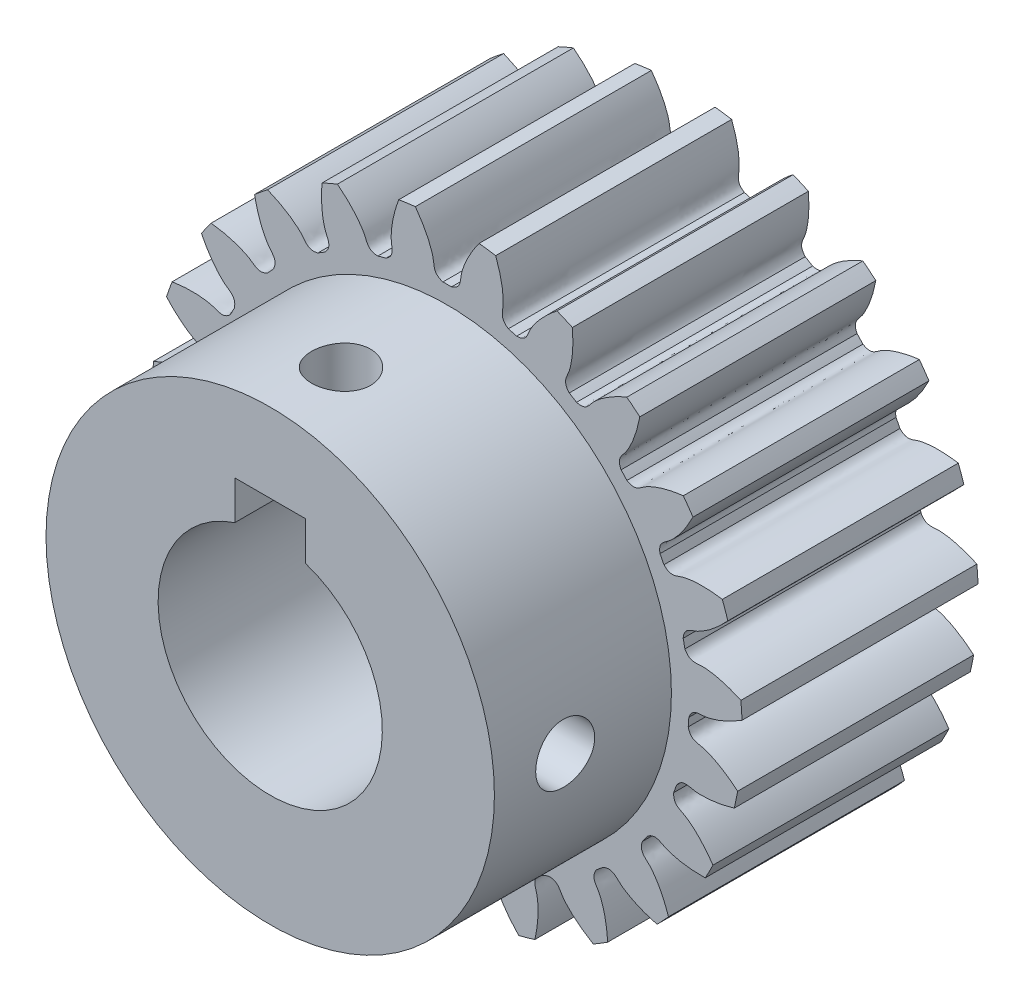
SolidWorks part; units mm, degrees
material "A3钢"
ref_plane "前视基准面" through (0, 0, 0) normal (0, 0, 1) x (1, 0, 0)
ref_plane "上视基准面" through (0, 0, 0) normal (0, 1, 0) x (1, 0, 0)
ref_plane "右视基准面" through (0, 0, 0) normal (1, 0, 0) x (0, 0, -1)
sketch "草图1" plane through (0, 0, 0) normal (0, 0, 1) x (1, 0, 0)
  circle A0 centre (0, 0) radius 25
extrude "凸台-拉伸1" add sketch "草图1" along normal blind 20
ref_axis "基准轴1" through (0, 0, 20) along (0, 0, -1)
sketch "草图2" plane through (0, 0, 0) normal (0, 0, 1) x (1, 0, 0)
  line L0 (0, 0) -> (0, 25) construction
  circle A0 centre (0, 0) radius 25 construction
  arc A1 (0.3628, 20.4968) -> (-0.3628, 20.4968) centre (0, 0) ccw
  arc A2 (6.3634, 28.3724) -> (-6.3634, 28.3724) centre (0, 0) ccw
  spline S0 degree 3 poles (0.3628, 20.4968) (1.1555, 20.7335) (1.0875, 21.2677) (1.1859, 21.7944) (1.199, 21.8578) (1.2153, 21.9295) (1.2352, 22.0092) (1.2588, 22.0968) (1.2867, 22.1923) (1.319, 22.2954) (1.3562, 22.4061) (1.3984, 22.5241) (1.4461, 22.6493) (1.4995, 22.7816) (1.5589, 22.9207) (1.6247, 23.0665) (1.6971, 23.2188) (1.7763, 23.3773) (1.8628, 23.5419) (1.9567, 23.7122) (2.0583, 23.8882) (2.1678, 24.0695) (2.2856, 24.2558) (2.4119, 24.447) (2.5468, 24.6427) (2.6907, 24.8428) (2.8438, 25.0468) (3.0062, 25.2545) (3.1782, 25.4657) (3.36, 25.6799) (3.5517, 25.897) (3.7537, 26.1165) (3.9659, 26.3382) (4.1886, 26.5618) (4.422, 26.7868) (4.6662, 27.013) (4.9213, 27.24) (5.1875, 27.4675) (5.4648, 27.6952) (5.8542, 28.0019) (6.1566, 28.2256) (6.3634, 28.3724) knots 0 0 0 0 0.147387 0.15296 0.159389 0.166677 0.174821 0.183823 0.193683 0.204399 0.215973 0.228404 0.241693 0.255839 0.270842 0.286703 0.303421 0.320996 0.339428 0.358718 0.378866 0.39987 0.421732 0.444451 0.468028 0.492462 0.517753 0.543901 0.570907 0.59877 0.627491 0.657069 0.687504 0.718796 0.750946 0.783953 0.817818 0.85254 0.888119 0.924555 1 1 1 1
  spline S1 degree 3 poles (-0.3628, 20.4968) (-1.1555, 20.7335) (-1.0875, 21.2677) (-1.1859, 21.7944) (-1.199, 21.8578) (-1.2153, 21.9295) (-1.2352, 22.0092) (-1.2588, 22.0968) (-1.2867, 22.1923) (-1.319, 22.2954) (-1.3562, 22.4061) (-1.3984, 22.5241) (-1.4461, 22.6493) (-1.4995, 22.7816) (-1.5589, 22.9207) (-1.6247, 23.0665) (-1.6971, 23.2188) (-1.7763, 23.3773) (-1.8628, 23.5419) (-1.9567, 23.7122) (-2.0583, 23.8882) (-2.1678, 24.0695) (-2.2856, 24.2558) (-2.4119, 24.447) (-2.5468, 24.6427) (-2.6907, 24.8428) (-2.8438, 25.0468) (-3.0062, 25.2545) (-3.1782, 25.4657) (-3.36, 25.6799) (-3.5517, 25.897) (-3.7537, 26.1165) (-3.9659, 26.3382) (-4.1886, 26.5618) (-4.422, 26.7868) (-4.6662, 27.013) (-4.9213, 27.24) (-5.1875, 27.4675) (-5.4648, 27.6952) (-5.8542, 28.0019) (-6.1566, 28.2256) (-6.3634, 28.3724) knots 0 0 0 0 0.147387 0.15296 0.159389 0.166677 0.174821 0.183823 0.193683 0.204399 0.215973 0.228404 0.241693 0.255839 0.270842 0.286703 0.303421 0.320996 0.339428 0.358718 0.378866 0.39987 0.421732 0.444451 0.468028 0.492462 0.517753 0.543901 0.570907 0.59877 0.627491 0.657069 0.687504 0.718796 0.750946 0.783953 0.817818 0.85254 0.888119 0.924555 1 1 1 1
extrude "切除-拉伸1" cut sketch "草图2" along normal through all
pattern_circular "阵列(圆周)1" count 23 every 15.652 about axis through (0, 0, 20) along (0, 0, -1) of "切除-拉伸1"
sketch "草图3" plane through (0, 0, 0) normal (0, 0, 1) x (1, 0, 0)
  circle A0 centre (0, 0) radius 23 construction
  dimension "Dn" = 46
sketch "草图4" plane through (0, 0, 20) normal (0, 0, 1) x (1, 0, 0)
  circle A0 centre (0, 0) radius 19
  dimension "D1" = 38
extrude "凸台-拉伸2" add sketch "草图4" along normal blind 15
sketch "草图5" plane through (0, 0, 35) normal (0, 0, 1) x (1, 0, 0)
  circle A0 centre (0, 0) radius 9.5
  dimension "D1" = 19
extrude "切除-拉伸2" cut sketch "草图5" against normal through all
sketch "草图6" plane through (0, 0, 35) normal (0, 0, 1) x (1, 0, 0)
  line L0 (0, 44.7067) -> (0, -43.9033) construction
  line L1 (-50.1471, 0) -> (55.6133, 0) construction
  line L3 (-3, 0) -> (3, 0)
  line L4 (-3, 0) -> (-3, 12.3)
  line L5 (-3, 12.3) -> (3, 12.3)
  line L6 (3, 0) -> (3, 12.3)
  line L7 (-3, 0) -> (3, 12.3) construction
  line L8 (-3, 12.3) -> (3, 0) construction
  circle A0 centre (0, 0) radius 9.5 construction
  point P5 (0, 6.15)
  dimension "D1" = 6
  dimension "D2" = 21.8
extrude "切除-拉伸3" cut sketch "草图6" against normal through all
ref_plane "基准面1" through (19, 0, 0) normal (1, 0, 0) x (0, 0, -1)
hole_wizard "M6 螺纹孔1" positions "草图7" profile "草图9" tap size "M6" standard "GB" end condition up to next
sketch "草图7" plane through (19, 0, 0) normal (1, 0, 0) x (0, 0, -1)
  line L0 (-35, 19) -> (-35, -19) construction
  line L1 (0, 0) -> (-55.7763, 0) construction
  point P0 (-29, 0)
  dimension "D1" = 6
sketch "草图9" plane through (19, 0, 29) normal (0, 1, 0) x (0, 0, -1)
  line L0 (0, 0) -> (0, 38)
  line L1 (0, 38) -> (2.5, 38)
  line L2 (2.5, 38) -> (2.5, 0)
  line L5 (2.5, 0) -> (0, 0)
  line L11 (0, -6.35) -> (0, 107.95) construction
  dimension "通孔螺纹孔钻头直径" = 5
  dimension "通孔螺纹孔钻头深度" = 38
cosmetic thread "孔螺蚊线1" parameters "D2"=6
pattern_circular "阵列(圆周)2" count 2 over 90 about axis through (0, 0, 35) along (0, 0, -1) of "M6 螺纹孔1" reverse direction yes
